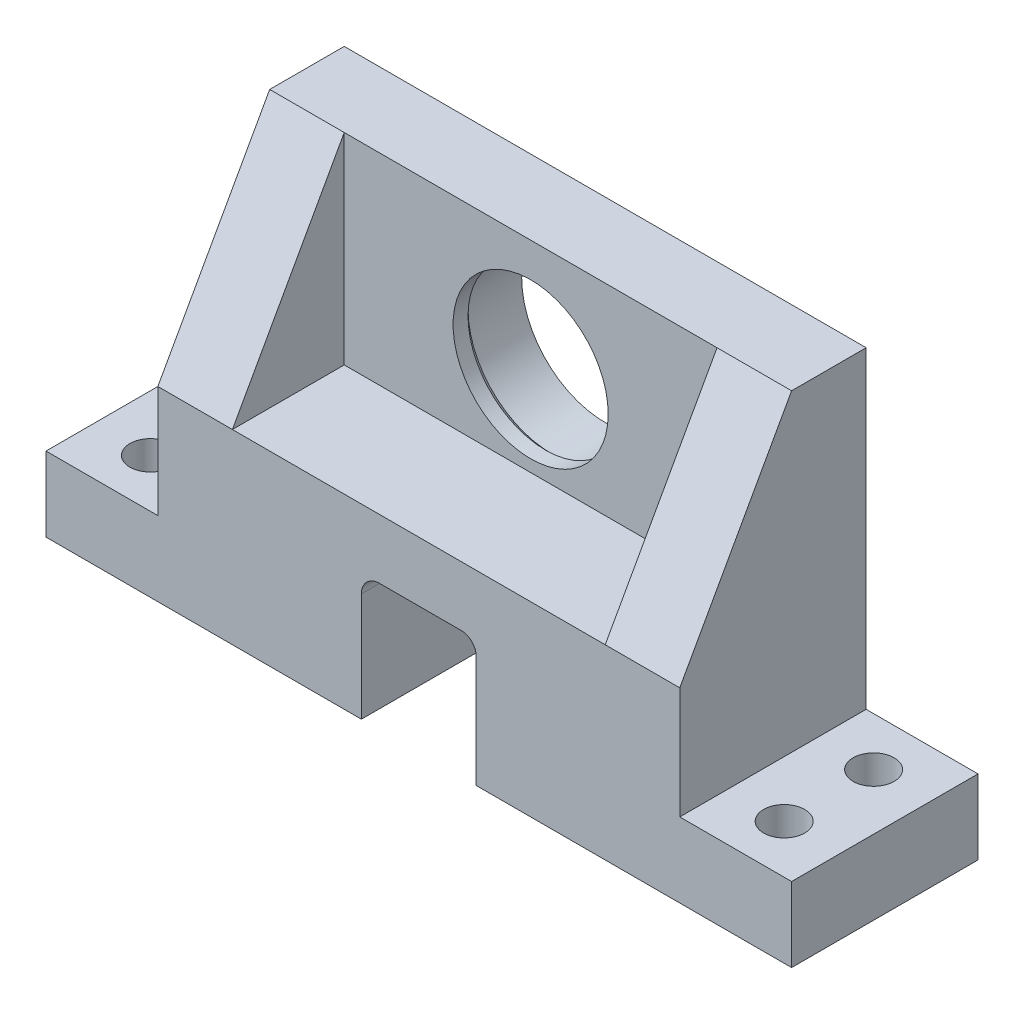
SolidWorks part; units mm, degrees
ref_plane "Front Plane" through (0, 0, 0) normal (0, 0, 1) x (1, 0, 0)
ref_plane "Top Plane" through (0, 0, 0) normal (0, 1, 0) x (1, 0, 0)
ref_plane "Right Plane" through (0, 0, 0) normal (1, 0, 0) x (0, 0, -1)
sketch "Sketch1" plane through (0, 0, 0) normal (0, 0, 1) x (1, 0, 0)
  line L1 (50, 0) -> (50, 10)
  line L2 (50, 10) -> (35, 10)
  line L5 (0, 0) -> (0, 37) construction
  line L12 (-50, 10) -> (-35, 10)
  line L13 (-50, 0) -> (-50, 10)
  line L14 (5.7, 17) -> (-5.2601, 17)
  line L15 (-35, 10) -> (-35, 52)
  line L16 (-35, 52) -> (35, 52)
  line L17 (35, 52) -> (35, 10)
  line L18 (-7.7, 0) -> (-7.7, 14.5601)
  line L19 (7.7, 0) -> (7.7, 15)
  line L20 (-7.7, 0) -> (-50, 0)
  line L21 (7.7, 0) -> (50, 0)
  arc A2 (7.7, 15) -> (5.7, 17) centre (5.7, 15) ccw
  arc A3 (-7.7, 14.5601) -> (-5.2601, 17) centre (-5.2601, 14.5601) cw
  dimension "D1" = 2
  dimension "D2" = 2.4399
  dimension "D3" = 15.4
extrude "Boss-Extrude1" add sketch "Sketch1" along normal blind 25
sketch "Sketch2" plane through (0, 0, 0) normal (0, 0, -1) x (-1, 0, 0)
  circle A0 centre (0, 37) radius 11.2
extrude "Cut-Extrude1" cut sketch "Sketch2" against normal through all
sketch "Sketch4" plane through (0, 10, 0) normal (0, 1, 0) x (1, 0, 0)
  line L0 (-42.5, 0) -> (-42.5, -6.5) construction
  line L3 (-35, 0) -> (-50, 0) construction
  line L4 (-42.5, -25) -> (-42.5, -18.5) construction
  line L5 (-35, -25) -> (-50, -25) construction
  line L6 (42.5, 0) -> (42.5, -6.5) construction
  line L7 (50, 0) -> (35, 0) construction
  line L8 (42.5, -25) -> (42.5, -18.5) construction
  line L9 (50, -25) -> (35, -25) construction
  point P2 (0, 0)
  point P3 (0, 0)
  point P6 (0, 0)
  point P7 (0, 0)
sketch "Sketch11" plane through (0, 0, 25) normal (0, 0, 1) x (1, 0, 0)
  line L1 (-45, 55) -> (45, 55)
  line L2 (-45, 55) -> (-45, 25)
  line L3 (-45, 25) -> (45, 25)
  line L4 (45, 55) -> (45, 25)
  line L5 (-45, 55) -> (45, 25) construction
  line L6 (-45, 25) -> (45, 55) construction
  point P0 (0, 37)
extrude "Cut-Extrude4" cut sketch "Sketch11" against normal blind 15
sketch "Sketch12" plane through (-35, 0, 0) normal (-1, 0, 0) x (0, 0, 1)
  line L0 (10, 52) -> (10, 25)
  line L1 (10, 25) -> (25, 25)
  line L2 (25, 25) -> (10, 52)
extrude "Boss-Extrude2" add sketch "Sketch12" against normal blind 10
sketch "Sketch13" plane through (35, 0, 0) normal (1, 0, 0) x (0, 0, -1)
  line L0 (-10, 52) -> (-10, 25)
  line L1 (-10, 25) -> (-25, 25)
  line L2 (-25, 25) -> (-10, 52)
extrude "Boss-Extrude3" add sketch "Sketch13" against normal blind 10
sketch "Sketch14" plane through (0, 0, 10) normal (0, 0, 1) x (1, 0, 0)
  circle A0 centre (0, 37) radius 11.4
  circle A1 centre (0, 37) radius 10.4
extrude "Boss-Extrude4" add sketch "Sketch14" against normal blind 3
chamfer "Chamfer1" distance 1 angle 45 1 edges at (10.4, 37, 7)
hole_wizard "M5 Clearance Hole1" positions "Sketch15" profile "Sketch16" hole size "M5" standard "ISO" end condition up to next
sketch "Sketch15" plane through (0, 10, 0) normal (0, 1, 0) x (1, 0, 0)
  point P0 (42.5, -18.5)
  point P3 (42.5, -6.5)
  point P6 (-42.5, -18.5)
  point P9 (-42.5, -6.5)
sketch "Sketch16" plane through (42.5, 10, 18.5) normal (1, 0, 0) x (0, 0, 1)
  line L0 (0, 0) -> (0, 10)
  line L1 (0, 10) -> (2.75, 10)
  line L2 (2.75, 10) -> (2.75, 0)
  line L5 (2.75, 0) -> (0, 0)
  line L11 (0, -6.35) -> (0, 107.95) construction
  dimension "Thru Hole Dia." = 5.5
  dimension "Thru Hole Depth" = 10
